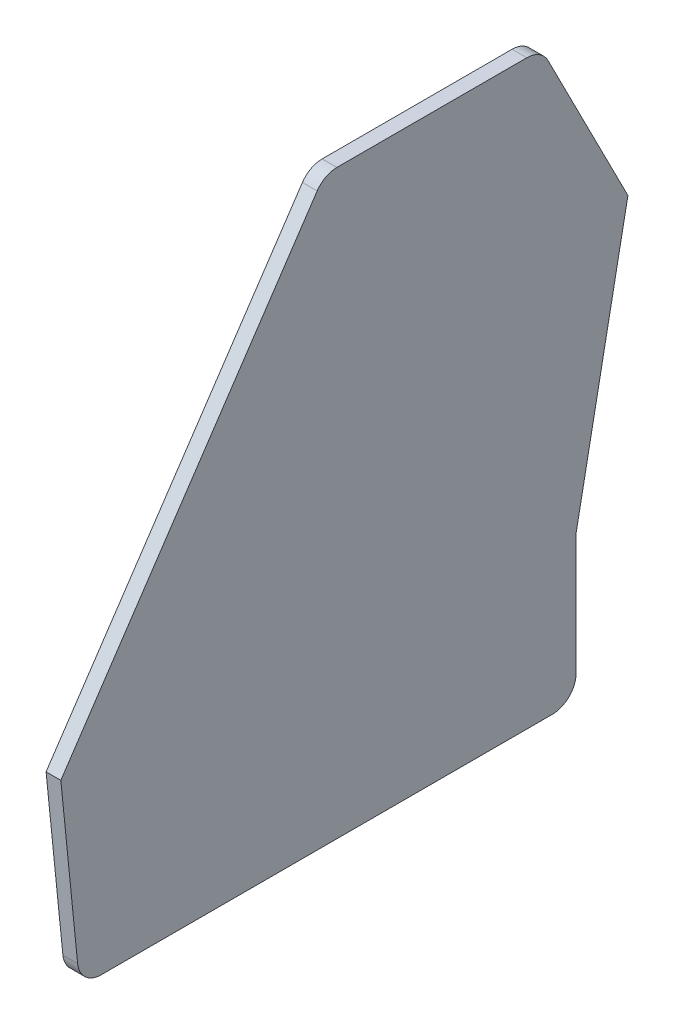
SolidWorks part; units mm, degrees
ref_plane "Front Plane" through (0, 0, 0) normal (0, 0, 1) x (1, 0, 0)
ref_plane "Top Plane" through (0, 0, 0) normal (0, 1, 0) x (1, 0, 0)
ref_plane "Right Plane" through (0, 0, 0) normal (1, 0, 0) x (0, 0, -1)
sketch "Sketch2" plane through (0, 0, 0) normal (1, 0, 0) x (0, 0, -1)
  line L0 (0, 0) -> (53.0352, 0)
  line L1 (53.0352, 0) -> (53.0352, 15.4991)
  line L2 (53.0352, 15.4991) -> (58.5724, 43.9855)
  line L3 (58.5724, 43.9855) -> (49.3281, 62.1284)
  line L4 (49.3281, 62.1284) -> (26.119, 62.1284)
  line L5 (4.6199, 33.2035) -> (-2.0282, 20.1559) construction
  line L6 (-2.0282, 20.1559) -> (0, 0)
  line L7 (26.119, 62.1284) -> (-2.0282, 20.1559)
  dimension "D1" = 53.0352
  dimension "D2" = 62.1284
  dimension "D5" = 63
  dimension "D6" = 62.6819
  dimension "D7" = 15.4991
  dimension "D8" = 38
extrude "Boss-Extrude1" add sketch "Sketch2" along normal blind 1.5748
sketch "Sketch3" plane through (1.5748, 0, 0) normal (1, 0, 0) x (0, 0, -1)
  line L0 (26.5176, 0) -> (26.5176, 6.4762) construction
  line L1 (0, 0) -> (53.0352, 0) construction
  line L2 (-2.0282, 20.1559) -> (0, 0) construction
  circle A0 centre (2.4257, 2.4257) radius 1.6891
  circle A1 centre (50.6095, 2.4257) radius 1.6891
  circle A2 centre (6.7681, 27.3685) radius 1.6891
  circle A3 centre (27.8699, 26.7081) radius 1.6891
  circle A4 centre (7.8245, 31.5707) radius 4.0005
  dimension "D1" = 3.3782
  dimension "D10" = 8.001
  dimension "D2" = 24.0919
  dimension "D3" = 24.0919
  dimension "D4" = 2.4257
  dimension "D5" = 2.4257
  dimension "D6" = 27.3685
  dimension "D7" = 26.7081
  dimension "D8" = 9.4742
  dimension "D9" = 30.4038
extrude "Cut-Extrude1" cut sketch "Sketch3" against normal through all rebuild error yes
fillet "Fillet1" radius 2.54 1 edges at (0.7874, 0, 0)
fillet "Fillet2" radius 2.54 3 edges at (0.7874, 0, -53.0352) (0.7874, 62.1284, -49.3281) (0.7874, 62.1284, -26.119)
scale "Scale1" scale about centroid uniform scaling yes scale factor 0.6
